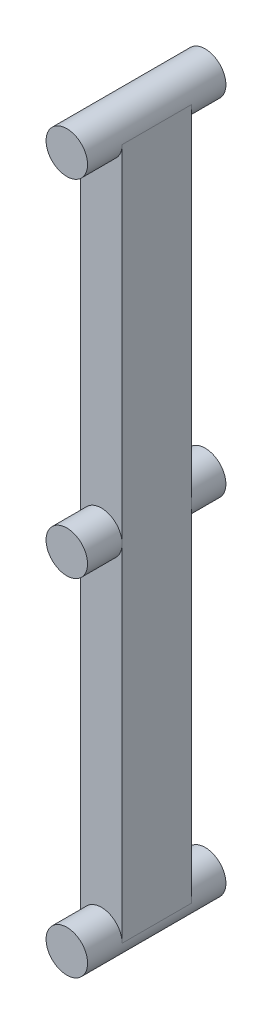
SolidWorks part; units mm, degrees
ref_plane "Alzado" through (0, 0, 0) normal (0, 0, 1) x (1, 0, 0)
ref_plane "Planta" through (0, 0, 0) normal (0, 1, 0) x (1, 0, 0)
ref_plane "Vista lateral" through (0, 0, 0) normal (1, 0, 0) x (0, 0, -1)
sketch "Croquis1" plane through (0, 0, 0) normal (0, 0, 1) x (1, 0, 0)
  line L1 (-1.5, -25) -> (1.5, -25)
  line L2 (-1.5, -25) -> (-1.5, 25)
  line L3 (-1.5, 25) -> (1.5, 25)
  line L4 (1.5, -25) -> (1.5, 25)
  line L5 (-1.5, -25) -> (1.5, 25) construction
  line L6 (-1.5, 25) -> (1.5, -25) construction
  circle A0 centre (0, 25) radius 1.5
  circle A1 centre (0, -25) radius 1.5
  circle A2 centre (0, 0) radius 1.5
  point P0 (0, 0)
  dimension "D1" = 3
  dimension "D2" = 50
extrude "Saliente-Extruir1" add sketch "Croquis1" along normal blind 2.5 and the other way blind 2.5 contours L3 L4 L1 L2
extrude "Saliente-Extruir2" add sketch "Croquis1<3>" along normal blind 5 and the other way blind 5 contours A2 | A1 | A0
sketch "Croquis1<3>" plane through (0, 0, 0) normal (0, 0, 1) x (1, 0, 0) same geometry as "Croquis1"
